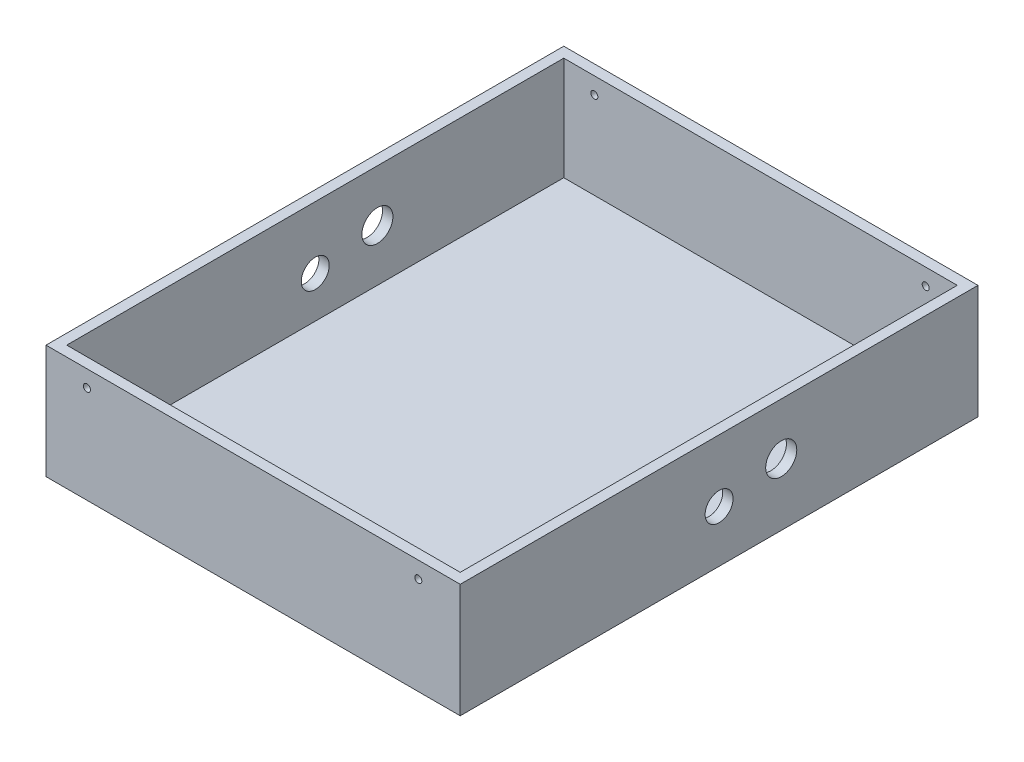
SolidWorks part; units mm, degrees
ref_plane "Front Plane" through (0, 0, 0) normal (0, 0, 1) x (1, 0, 0)
ref_plane "Top Plane" through (0, 0, 0) normal (0, 1, 0) x (1, 0, 0)
ref_plane "Right Plane" through (0, 0, 0) normal (1, 0, 0) x (0, 0, -1)
sketch "Sketch1" plane through (0, 0, 0) normal (0, 0, 1) x (1, 0, 0)
  line L0 (0, 50) -> (0, 0) construction
  line L1 (-95, 0) -> (95, 0)
  line L2 (-95, 0) -> (-95, 50)
  line L3 (-95, 50) -> (95, 50)
  line L4 (95, 0) -> (95, 50)
  dimension "D1" = 190
  dimension "D2" = 50
extrude "Boss-Extrude1" add sketch "Sketch1" along normal mid plane 240
shell "Shell1" thickness 5 removed face at (0, 50, 0) outward yes
sketch "Sketch3" plane through (100, 0, 0) normal (1, 0, 0) x (0, 0, -1)
  line L0 (-125, -5) -> (125, -5) construction
  line L1 (-15, -5) -> (15, -5)
  line L2 (-15, -5) -> (-15, 30)
  line L3 (-15, 30) -> (15, 30) construction
  line L4 (15, -5) -> (15, 30)
  line L5 (0, 30) -> (0, 20) construction
  line L6 (9.0631, 24.2262) -> (-0.618, 44.9873)
  line L7 (-15, 28.5056) -> (-9.0631, 15.7738)
  circle A0 centre (0, 20) radius 6.75
  arc A1 (-15, 30) -> (15, 30) centre (0, 30) cw
  circle A2 centre (0, 20) radius 10
  dimension "D2" = 13.5
  dimension "D5" = 20
  dimension "D1" = 25
  dimension "D3" = 30
  dimension "D4" = 10
  dimension "D6" = 25
extrude "Cut-Extrude2" cut sketch "Sketch3" against normal through all both and the other way through all contours A0 region at (100, 20, 0)
hole_wizard "M3 Clearance Hole1" positions "Sketch4" profile "Sketch5" hole size "M3" standard "ANSI Metric" end condition through all
sketch "Sketch4" plane through (0, 0, 125) normal (0, 0, 1) x (1, 0, 0)
  point P0 (-80.25, 42)
  point P1 (79.75, 42)
sketch "Sketch5" plane through (-80.25, 42, 125) normal (1, 0, 0) x (0, -1, 0)
  line L0 (0, 0) -> (0, 250)
  line L1 (0, 250) -> (1.7, 250)
  line L2 (1.7, 250) -> (1.7, 0)
  line L3 (1.7, 0) -> (0, 0)
  line L4 (0, -6.35) -> (0, 107.95) construction
  dimension "Thru Hole Dia." = 3.4
  dimension "Thru Hole Depth" = 250
sketch "Sketch8" plane through (0, 0, 0) normal (1, 0, 0) x (0, 0, -1)
  circle A0 centre (30, 25) radius 7.5
  dimension "D1" = 15
  dimension "D2" = 25
  dimension "D3" = 30
extrude "Cut-Extrude4" cut sketch "Sketch8" against normal through all both and the other way through all
